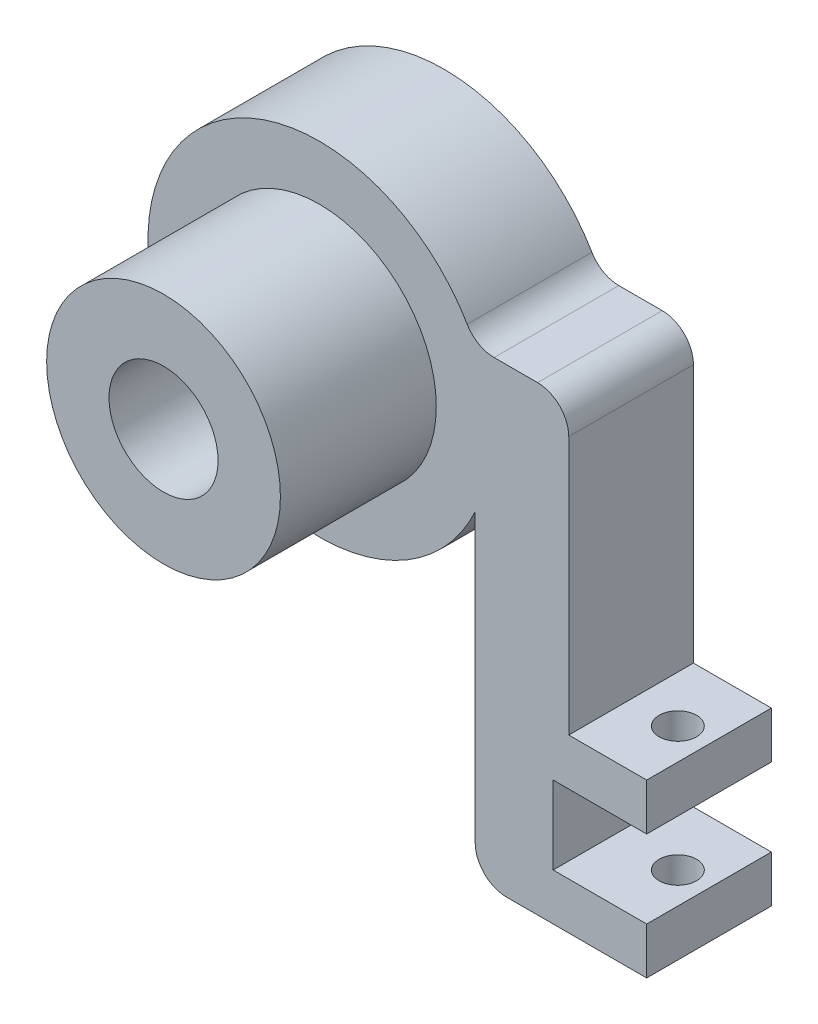
SolidWorks part; units mm, degrees
ref_plane "Plan de face" through (0, 0, 0) normal (0, 0, 1) x (1, 0, 0)
ref_plane "Plan de dessus" through (0, 0, 0) normal (0, 1, 0) x (1, 0, 0)
ref_plane "Plan de droite" through (0, 0, 0) normal (1, 0, 0) x (0, 0, -1)
sketch "Esquisse1" plane through (0, 0, 0) normal (0, 0, 1) x (1, 0, 0)
  line L1 (0, 0) -> (32, 0) construction
  line L2 (0, 0) -> (0, -36) construction
  line L3 (0, -36) -> (32, -36) construction
  line L4 (32, 0) -> (32, -36) construction
  line L5 (21, -6.4174) -> (27, -6.4174)
  line L7 (27, -6.4174) -> (27, -25)
  line L8 (32, -28) -> (32, -25)
  line L9 (32, -36) -> (21, -36)
  line L10 (32, -36) -> (32, -33)
  line L11 (32, -25) -> (27, -25)
  line L14 (21, -36) -> (21, -15.5826)
  line L17 (32, -33) -> (26, -33)
  line L19 (32, -28) -> (26, -28)
  line L20 (26, -33) -> (26, -28)
  line L21 (21, -6.4174) -> (21, -15.5826) construction
  arc A0 (21, -6.4174) -> (21, -15.5826) centre (11, -11) ccw
  point P6 (21, -11)
  point P20 (26, -30.5)
  dimension "D3" = 22
  dimension "D1" = 32
  dimension "D2" = 36
  dimension "D4" = 11
  dimension "D5" = 11
  dimension "D6" = 11
  dimension "D8" = 6
  dimension "D9" = 5
  dimension "D10" = 5.5
  dimension "D11" = 5
  dimension "D7" = 21
extrude "Boss.-Extru.1" add sketch "Esquisse1" along normal blind 8
sketch "Esquisse2" plane through (0, -25, 0) normal (0, 1, 0) x (1, 0, 0)
  line L0 (27, -8) -> (27, 0) construction
  line L1 (32, -8) -> (27, -8) construction
  circle A0 centre (30, -4) radius 1
  dimension "D1" = 2
  dimension "D2" = 3
  dimension "D3" = 4
extrude "Enlèv. mat.-Extru.1" cut sketch "Esquisse2" against normal up to surface (11 mm away) up to face at (26.5, -36, 4)
hole_wizard "Dégagement M21" positions "Esquisse3" profile "Esquisse4" hole size "M2" standard "ISO"
sketch "Esquisse3" plane through (0, -25, 0) normal (0, 1, 0) x (1, 0, 0)
  point P0 (30, -4)
sketch "Esquisse4" plane through (30, -25, 4) normal (1, 0, 0) x (0, 0, 1)
  line L0 (0, 0) -> (0, 11.721)
  line L1 (0, 11.721) -> (1.2, 11)
  line L2 (1.2, 11) -> (1.2, 0)
  line L5 (1.2, 0) -> (0, 0)
  line L10 (0, 11.721) -> (-1.2, 11) construction
  line L11 (0, -6.35) -> (0, 107.95) construction
  dimension "Diamètre du perçage" = 2.4
  dimension "Profondeur du perçage" = 11
  dimension "Angle de pointe" = 118
fillet "Congé1" radius 2 3 edges at (21, -36, 4) (21, -6.4174, 4) (27, -6.4174, 4)
sketch "Esquisse5" plane through (0, 0, 8) normal (0, 0, 1) x (1, 0, 0)
  circle A0 centre (11, -11) radius 7.5
  dimension "D1" = 15
extrude "Boss.-Extru.2" add sketch "Esquisse5" along normal blind 10
sketch "Esquisse6" plane through (0, 0, 0) normal (0, 0, -1) x (-1, 0, 0)
  line L0 (-11, -3.5) -> (-11, -18.5) construction
  line L1 (0, -4.0566) -> (0, -19.2348) construction
  line L2 (-19.6078, 0) -> (-3.8534, 0) construction
  circle A0 centre (-11, -3.5) radius 0.75
  circle A1 centre (-11, -18.5) radius 0.75
  arc A2 (-21, -15.5826) -> (-20.4856, -5.4301) centre (-11, -11) ccw construction
  circle A3 centre (-11, -11) radius 3.5 construction
  point P7 (-11, -2.2579)
  point P8 (-11, -11)
  dimension "D2" = 1.5
  dimension "D3" = 1.5
  dimension "D5" = 7
  dimension "D1" = 11
  dimension "D4" = 11
  dimension "D6" = 15
extrude "Enlèv. mat.-Extru.2" cut sketch "Esquisse6" against normal offset from surface (6 mm away) 2 up to face at (18.5, -11, 8)
sketch "Esquisse8" plane through (0, 0, 0) normal (0, 0, -1) x (-1, 0, 0)
  circle A0 centre (-11, -11) radius 3.5
  dimension "D1" = 7
extrude "Enlèv. mat.-Extru.3" cut sketch "Esquisse8" against normal up to surface (18 mm away) up to face at (18.5, -11, 18)
equation "\"D4@Esquisse1\"=\"D3@Esquisse1\"/2"
equation "\"D5@Esquisse1\"=\"D3@Esquisse1\"/2"
equation "\"D10@Esquisse1\"=\"D6@Esquisse1\"/2"
